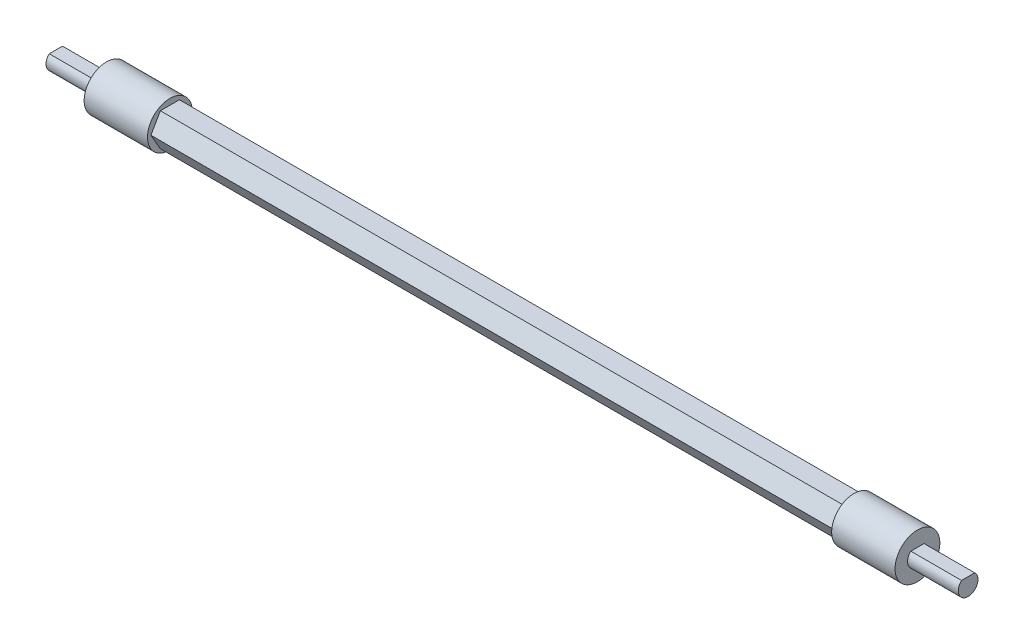
SolidWorks part; units mm, degrees
material "ABS"
ref_plane "Front Plane" through (0, 0, 0) normal (0, 0, 1) x (1, 0, 0)
ref_plane "Top Plane" through (0, 0, 0) normal (0, 1, 0) x (1, 0, 0)
ref_plane "Right Plane" through (0, 0, 0) normal (1, 0, 0) x (0, 0, -1)
sketch "Sketch1" plane through (0, 0, 0) normal (1, 0, 0) x (0, 0, -1)
  line L1 (3.75, 0) -> (1.875, 3.2476)
  line L2 (1.875, 3.2476) -> (-1.875, 3.2476)
  line L3 (-1.875, 3.2476) -> (-3.75, 0)
  line L4 (-3.75, 0) -> (-1.875, -3.2476)
  line L5 (-1.875, -3.2476) -> (1.875, -3.2476)
  line L6 (1.875, -3.2476) -> (3.75, 0)
  circle A0 centre (0, 0) radius 3.75 construction
  circle A1 centre (0, 0) radius 4.425
  dimension "D1" = 8.85
  dimension "D2" = 7.5
extrude "Boss-Extrude1" add sketch "Sketch1" along normal mid plane 135 contours L1 A1 L2 L3 L4 L5 L6 | A1 L3 L4 | A1 L2 L3 | A1 L1 L2 | A1 L6 L1 | A1 L5 L6 | A1 L4 L5 region at (0, 0, 0)
extrude "Boss-Extrude2" add sketch "Sketch1<3>" along normal blind 12.5 from offset 67.5 contours L2 A1 | L1 A1 | L6 A1 | L5 A1 | L4 A1 | L3 A1 | L5 L6 L1 L2 L3 L4 region at (0, 0, 0) region at (0, 0, 4.2998)
sketch "Sketch1<3>" plane through (0, 0, 0) normal (1, 0, 0) x (0, 0, -1) same geometry as "Sketch1"
sketch "Sketch4" plane through (80, 0, 0) normal (1, 0, 0) x (0, 0, -1)
  line L0 (-1.3038, 1.45) -> (1.3038, 1.45)
  circle A1 centre (0, 0) radius 1.95
  circle A2 centre (0, 0) radius 4.425
  circle A3 centre (0, 0) radius 4.425
  dimension "D1" = 3.9
  dimension "D3" = 0.5
  dimension "D2" = 0
extrude "Boss-Extrude4" add sketch "Sketch4" along normal blind 10 contours L0 A1 region at (80, -0.1337, 0)
mirror "Mirror2" about plane through (0, 0, 0) normal (1, 0, 0) of "Boss-Extrude4", "Boss-Extrude2"
